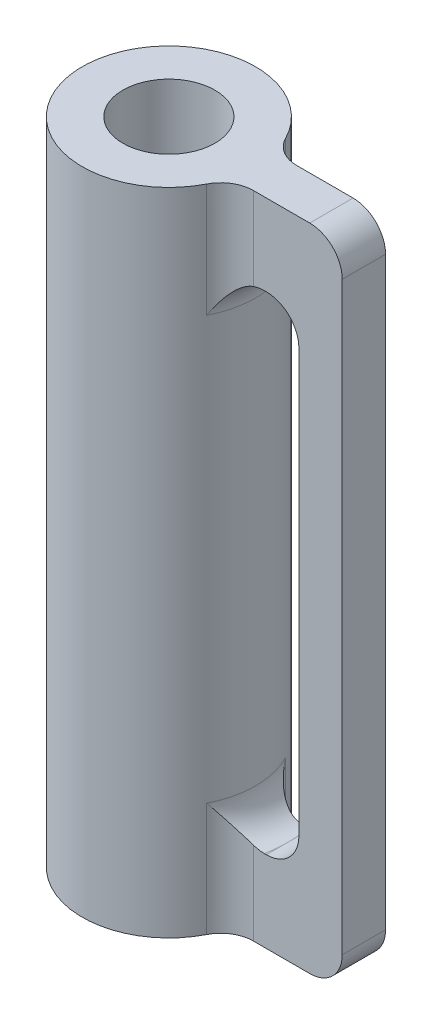
SolidWorks part; units mm, degrees
ref_plane "Front Plane" through (0, 0, 0) normal (0, 0, 1) x (1, 0, 0)
ref_plane "Top Plane" through (0, 0, 0) normal (0, 1, 0) x (1, 0, 0)
ref_plane "Right Plane" through (0, 0, 0) normal (1, 0, 0) x (0, 0, -1)
sketch "Sketch1" plane through (0, 0, 0) normal (0, 1, 0) x (1, 0, 0)
  circle A0 centre (0, 0) radius 8
  circle A1 centre (0, 0) radius 4.25
  dimension "D1" = 16
  dimension "D2" = 8.5
extrude "Boss-Extrude1" add sketch "Sketch1" along normal blind 60 contours A0 | A1
sketch "Sketch2" plane through (0, 0, 0) normal (0, 0, 1) x (1, 0, 0)
  line L0 (-8, 0) -> (-8, 55)
  line L1 (8, 60) -> (8, 0)
  line L2 (8, 60) -> (8, 0) construction
  line L3 (18, 60) -> (4.25, 60)
  line L5 (18, 0) -> (18, 60)
  line L8 (14, 7.5) -> (14, 52.5)
  line L16 (8, 0) -> (4.25, 0)
  line L17 (-4.25, 0) -> (-8, 0)
  line L19 (8, 0) -> (4.25, 0) construction
  line L20 (4.25, 60) -> (4.25, 52.5)
  line L21 (4.25, 52.5) -> (14, 52.5)
  line L22 (4.25, 0) -> (4.25, 7.5)
  line L23 (4.25, 7.5) -> (14, 7.5)
  line L24 (18, 0) -> (4.25, 0)
  point P10 (14, 30)
  point P12 (18, 30)
  dimension "D1" = 45
  dimension "D2" = 4
  dimension "D3" = 10
extrude "Boss-Extrude2" add sketch "Sketch2" along normal mid plane 4
fillet "Fillet1" radius 3 10 edges at (18, 0, 0) (18, 60, 0) (14, 7.5, 0) (14, 52.5, 0) (8, 52.5, 0) (7.746, 56.25, -2) (8, 7.5, 0) (7.746, 3.75, -2) (7.746, 3.75, 2) (7.746, 56.25, 2)
sketch "Sketch3" plane through (0, 0, 0) normal (0, -1, 0) x (1, 0, 0)
  circle A0 centre (0, 0) radius 6.25
  dimension "D1" = 12.5
extrude "Cut-Extrude1" cut sketch "Sketch3" against normal blind 30
